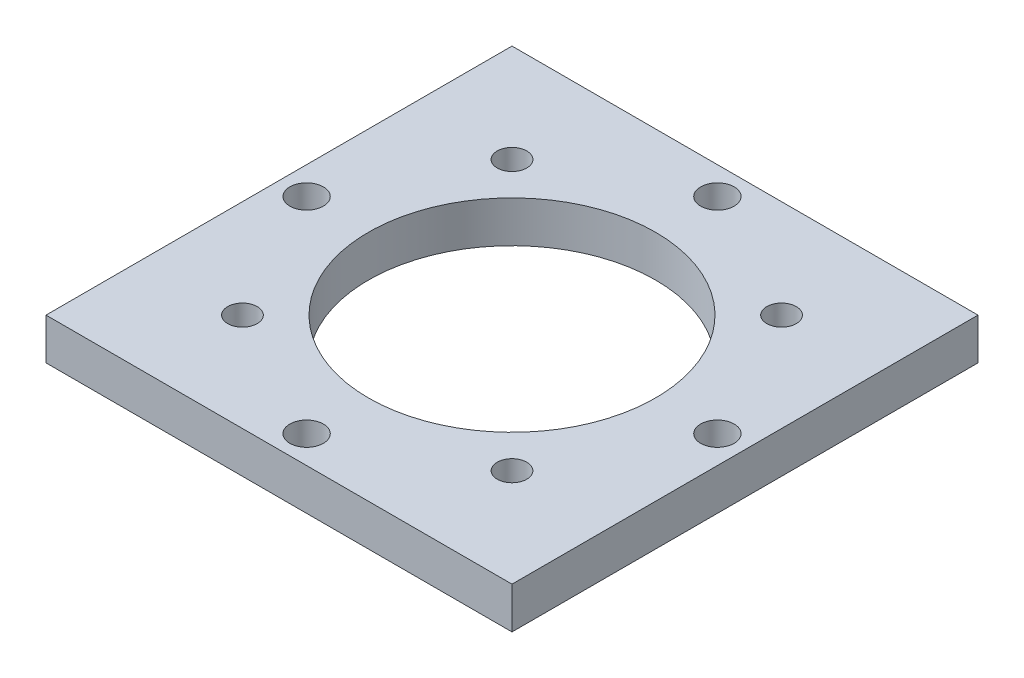
SolidWorks part; units mm, degrees
ref_plane "Front Plane" through (0, 0, 0) normal (0, 0, 1) x (1, 0, 0)
ref_plane "Top Plane" through (0, 0, 0) normal (0, 1, 0) x (1, 0, 0)
ref_plane "Right Plane" through (0, 0, 0) normal (1, 0, 0) x (0, 0, -1)
sketch "Sketch1" plane through (0, 0, 0) normal (0, 1, 0) x (1, 0, 0)
  line L1 (-15.5, -15.5) -> (15.5, -15.5) construction
  line L2 (-15.5, -15.5) -> (-15.5, 15.5) construction
  line L3 (-15.5, 15.5) -> (15.5, 15.5) construction
  line L4 (15.5, -15.5) -> (15.5, 15.5) construction
  line L5 (-15.5, -15.5) -> (15.5, 15.5) construction
  line L6 (-15.5, 15.5) -> (15.5, -15.5) construction
  line L7 (-23.622, -23.622) -> (23.622, -23.622) construction
  line L8 (-23.622, -23.622) -> (-23.622, 23.622) construction
  line L9 (-23.622, 23.622) -> (23.622, 23.622) construction
  line L10 (23.622, -23.622) -> (23.622, 23.622) construction
  line L11 (-23.622, -23.622) -> (23.622, 23.622) construction
  line L12 (-23.622, 23.622) -> (23.622, -23.622) construction
  line L13 (-26.797, -26.797) -> (26.797, -26.797)
  line L14 (-26.797, -26.797) -> (-26.797, 26.797)
  line L15 (-26.797, 26.797) -> (26.797, 26.797)
  line L16 (26.797, -26.797) -> (26.797, 26.797)
  line L17 (-26.797, -26.797) -> (26.797, 26.797) construction
  line L18 (-26.797, 26.797) -> (26.797, -26.797) construction
  circle A0 centre (0, 0) radius 16.51
  circle A1 centre (-15.5, 15.5) radius 1.7
  circle A2 centre (15.5, 15.5) radius 1.7
  circle A3 centre (15.5, -15.5) radius 1.7
  circle A4 centre (-15.5, -15.5) radius 1.7
  circle A5 centre (0, 23.622) radius 1.9266
  circle A6 centre (0, 0) radius 23.622 construction
  circle A7 centre (23.622, 0) radius 1.9266
  circle A8 centre (0, -23.622) radius 1.9266
  circle A9 centre (-23.622, 0) radius 1.9266
  point P0 (0, 0)
  point P31 (0, 0)
  dimension "D1" = 33.02
  dimension "D3" = 3.4
  dimension "D2" = 31
  dimension "D4" = 23.622
  dimension "D5" = 3.175
extrude "Boss-Extrude1" add sketch "Sketch1" along normal blind 4.7625
equation "\"D4@Sketch1\"=.93"
